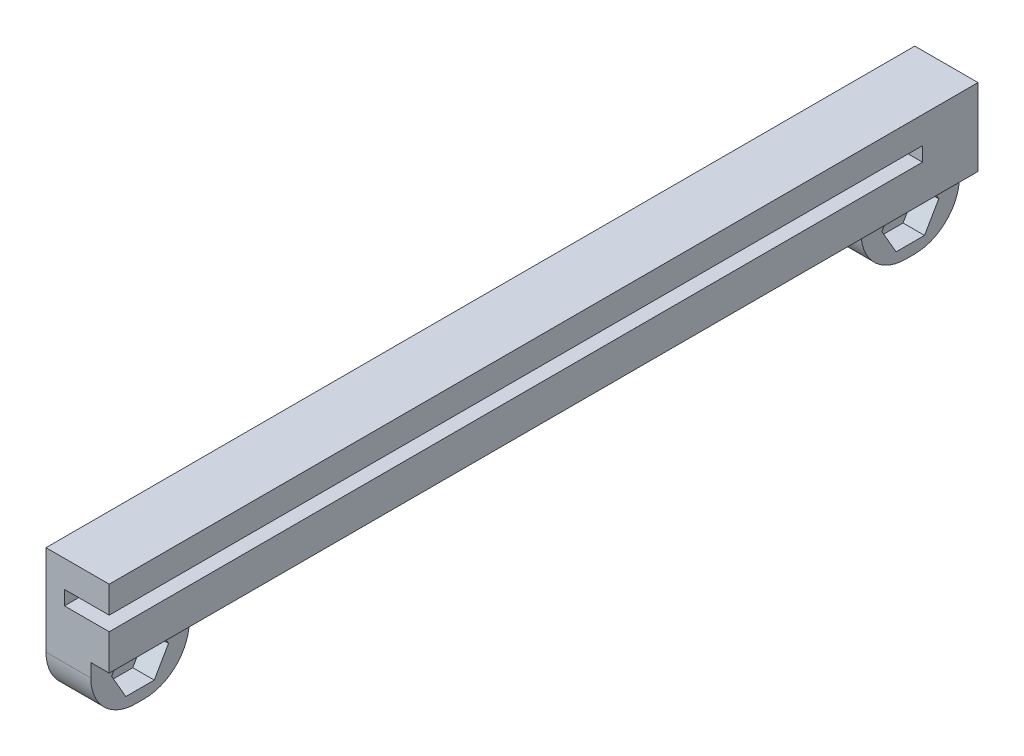
SolidWorks part; units mm, degrees
material "ABS"
ref_plane "Front Plane" through (0, 0, 0) normal (0, 0, 1) x (1, 0, 0)
ref_plane "Top Plane" through (0, 0, 0) normal (0, 1, 0) x (1, 0, 0)
ref_plane "Right Plane" through (0, 0, 0) normal (1, 0, 0) x (0, 0, -1)
sketch "Sketch1" plane through (0, 0, 0) normal (0, 1, 0) x (1, 0, 0)
  line L1 (-3.5288, -48.5) -> (3.5288, -48.5)
  line L2 (-3.5288, -48.5) -> (-3.5288, 48.5)
  line L3 (-3.5288, 48.5) -> (3.5288, 48.5)
  line L4 (3.5288, -48.5) -> (3.5288, 48.5)
  line L5 (-3.5288, -48.5) -> (3.5288, 48.5) construction
  line L6 (-3.5288, 48.5) -> (3.5288, -48.5) construction
  point P0 (0, 0)
  dimension "D1" = 97
  dimension "D2" = 7.0575
extrude "Boss-Extrude2" add sketch "Sketch1" along normal blind 7.6
sketch "Sketch4" plane through (0, 7.6, 0) normal (0, 1, 0) x (1, 0, 0)
  line L0 (3.5288, -48.5) -> (3.5288, 48.5) construction
  line L1 (3.5288, 42.305) -> (-1.4713, 42.305)
  line L2 (3.5288, 42.305) -> (3.5288, -48.5)
  line L3 (3.5288, -48.5) -> (-1.4713, -48.5)
  line L4 (-1.4713, 42.305) -> (-1.4713, -48.5)
  line L5 (-3.5288, -48.5) -> (3.5288, -48.5) construction
  line L7 (-3.5288, 48.5) -> (-3.5288, -48.5) construction
  dimension "D1" = 90.805
  dimension "D2" = 2.0575
extrude "Cut-Extrude1" cut sketch "Sketch4" against normal blind 4.6
sketch "Sketch6" plane through (0, 7.6, 0) normal (0, 1, 0) x (1, 0, 0)
  line L1 (3.5288, 42.305) -> (-1.4713, 42.305)
  line L2 (3.5288, 42.305) -> (3.5288, -48.5)
  line L3 (3.5288, -48.5) -> (-1.4713, -48.5)
  line L4 (-1.4713, 42.305) -> (-1.4713, -48.5)
extrude "Boss-Extrude3" add sketch "Sketch6" against normal blind 3
sketch "Sketch8" plane through (0, 0, 0) normal (0, -1, 0) x (1, 0, 0)
  line L1 (-3.5288, 48.5) -> (3.5287, 48.5)
  line L2 (-3.5288, 48.5) -> (-3.5287, -48.5)
  line L3 (-3.5287, -48.5) -> (3.5288, -48.5)
  line L4 (3.5287, 48.5) -> (3.5288, -48.5)
extrude "Boss-Extrude4" add sketch "Sketch8" along normal blind 1
sketch "Sketch9" plane through (0, -1, 0) normal (0, -1, 0) x (1, 0, 0)
  line L1 (-3.5288, 48.5) -> (1.4712, 48.5)
  line L2 (-3.5288, 48.5) -> (-3.5288, 37.5)
  line L3 (-3.5288, 37.5) -> (1.4712, 37.5)
  line L4 (1.4712, 48.5) -> (1.4712, 37.5)
  line L5 (-3.5287, -48.5) -> (1.4713, -48.5)
  line L6 (-3.5287, -48.5) -> (-3.5287, -37.5)
  line L7 (-3.5287, -37.5) -> (1.4713, -37.5)
  line L8 (1.4713, -48.5) -> (1.4713, -37.5)
  point P10 (1.4713, -43)
  dimension "D1" = 11
  dimension "D2" = 11
  dimension "D3" = 5
  dimension "D4" = 5
extrude "Boss-Extrude5" add sketch "Sketch9" along normal blind 6.5 contours L2 L1 L4 L3 | L6 L5 L8 L7
sketch "Sketch10" plane through (1.4713, 0, 0) normal (1, 0, 0) x (0, 0, -1)
  line L0 (-48.5, -7.5) -> (-48.5, -1) construction
  line L1 (-44.5877, -0.75) -> (-46.1754, -3.5)
  line L2 (-46.1754, -3.5) -> (-44.5877, -6.25)
  line L3 (-44.5877, -6.25) -> (-41.4123, -6.25)
  line L4 (-41.4123, -6.25) -> (-39.8246, -3.5)
  line L5 (-39.8246, -3.5) -> (-41.4123, -0.75)
  line L6 (-41.4123, -0.75) -> (-44.5877, -0.75)
  line L7 (-48.5, -7.5) -> (-37.5, -7.5) construction
  line L8 (37.5, -7.5) -> (37.5, -1) construction
  line L9 (46.1754, -3.5) -> (44.5877, -0.75)
  line L10 (44.5877, -0.75) -> (41.4123, -0.75)
  line L11 (41.4123, -0.75) -> (39.8246, -3.5)
  line L12 (39.8246, -3.5) -> (41.4123, -6.25)
  line L13 (41.4123, -6.25) -> (44.5877, -6.25)
  line L14 (44.5877, -6.25) -> (46.1754, -3.5)
  line L15 (48.5, -7.5) -> (37.5, -7.5) construction
  circle A0 centre (-43, -3.5) radius 2.75 construction
  circle A1 centre (43, -3.5) radius 2.75 construction
  dimension "D1" = 5.5
  dimension "D2" = 5.5
  dimension "D3" = 1.25
  dimension "D4" = 5.5
  dimension "D5" = 1.25
  dimension "D6" = 5.5
extrude "Cut-Extrude2" cut sketch "Sketch10" against normal blind 2.4
sketch "Sketch11" plane through (-0.9287, 0, 0) normal (1, 0, 0) x (0, 0, -1)
  line L2 (-48.5, -7.5) -> (-37.5, -7.5) construction
  line L3 (-48.5, -7.5) -> (-48.5, -1) construction
  line L4 (37.5, -7.5) -> (37.5, -1) construction
  line L5 (48.5, -7.5) -> (37.5, -7.5) construction
  circle A0 centre (-43, -3.5) radius 1.6
  circle A1 centre (43, -3.5) radius 1.6
  dimension "D3" = 3.2
  dimension "D4" = 3.2
  dimension "D1" = 4
  dimension "D2" = 5.5
  dimension "D5" = 5.5
  dimension "D6" = 4
extrude "Cut-Extrude3" cut sketch "Sketch11" against normal through all contours A0 | A1
fillet "Fillet2" radius 5 4 edges at (-1.0287, -7.5, -48.5) (-1.0287, -7.5, -37.5) (-1.0288, -7.5, 37.5) (-1.0288, -7.5, 48.5)
mirror "Mirror2" [suppressed] of bodies 109
delete or keep bodies "Body-Delete/Keep 1" [suppressed] type delete bodies bodies 109
